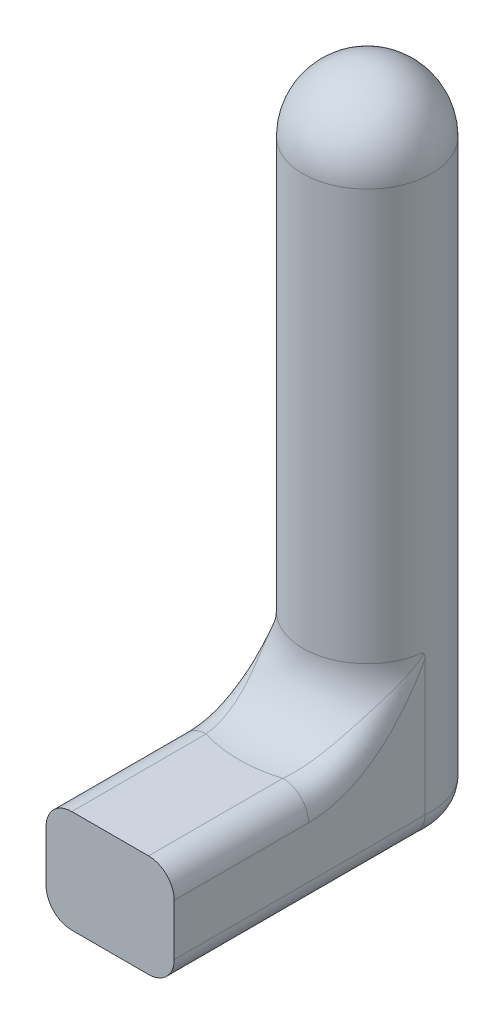
SolidWorks part; units mm, degrees
material "PET"
ref_plane "Спереди" through (0, 0, 0) normal (0, 0, 1) x (1, 0, 0)
ref_plane "Сверху" through (0, 0, 0) normal (0, 1, 0) x (1, 0, 0)
ref_plane "Справа" through (0, 0, 0) normal (1, 0, 0) x (0, 0, -1)
other "Configuration Table"
sketch "Эскиз1" plane through (0, 0, 0) normal (0, 1, 0) x (1, 0, 0)
  circle A0 centre (0, 0) radius 1
extrude "Бобышка-Вытянуть1" add sketch "Эскиз1" along normal blind 10
sketch "Эскиз2" plane through (0, 0, 0) normal (0, -1, 0) x (1, 0, 0)
  line L1 (-1, 0) -> (0.9954, 0)
  line L2 (-1, 0) -> (-1, 4)
  line L3 (-1, 4) -> (0.9954, 4)
  line L4 (0.9954, 0) -> (0.9954, 4)
  line L5 (-0.0023, 4) -> (-0.0023, 0) construction
  line L6 (-1, 2) -> (0.9954, 2) construction
  circle A0 centre (0, 0) radius 1 construction
  point P528 (-0.0023, 2)
  dimension "D1" = 4
extrude "Бобышка-Вытянуть2" add sketch "Эскиз2" against normal blind 1.6
fillet "Скругление2" radius 1 1 edges at (-0.0478, 1.6, 0.9989)
fillet "Скругление4" radius 1 1 edges at (0, 10, 1)
fillet "Скругление5" radius 0.4 7 edges at (0.0478, 0, -0.9989) (-1, 1.6894, 1.2321) (0.9954, 2.4783, 0.155) (-1, 0, 2) (-1, 1.6, 2.866) (0.9954, 0, 2.0477) (0.9954, 1.6, 2.8673)
